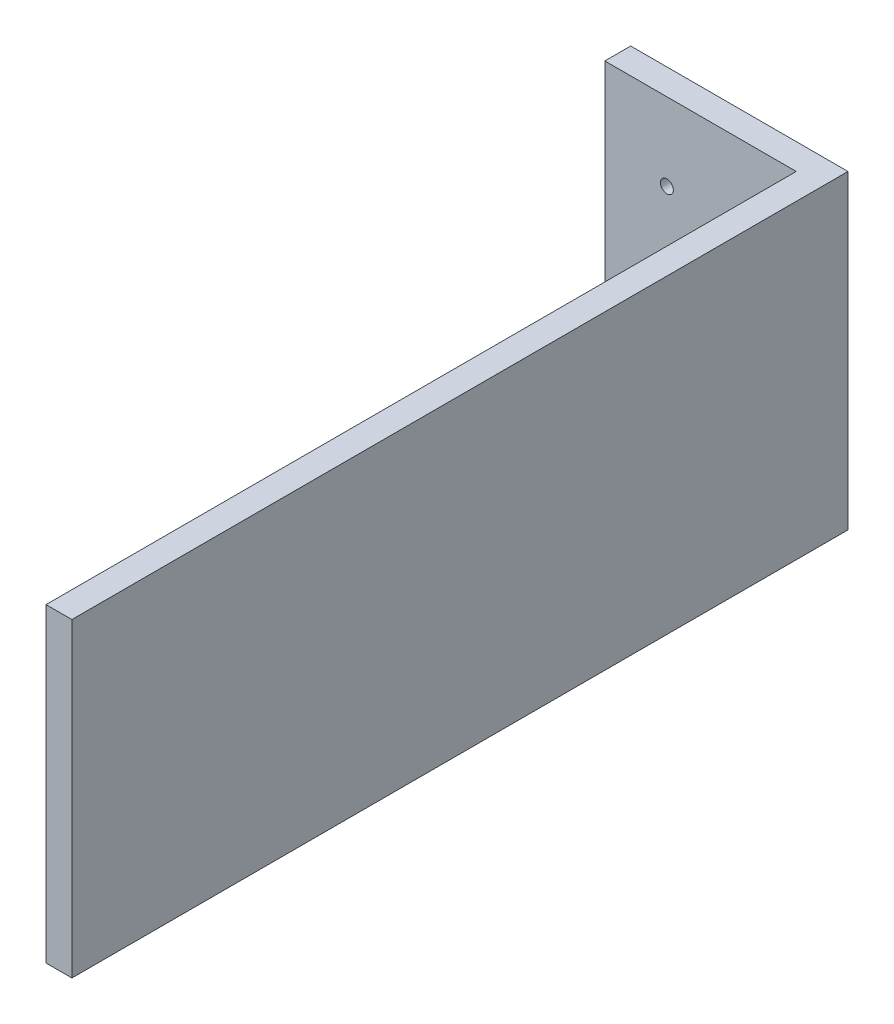
SolidWorks part; units mm, degrees
ref_plane "前视基准面" through (0, 0, 0) normal (0, 0, 1) x (1, 0, 0)
ref_plane "上视基准面" through (0, 0, 0) normal (0, 1, 0) x (1, 0, 0)
ref_plane "右视基准面" through (0, 0, 0) normal (1, 0, 0) x (0, 0, -1)
sketch "草图1" plane through (0, 0, 0) normal (0, 0, 1) x (1, 0, 0)
  line L0 (-788.4059, 0) -> (38631.8872, 0) construction
  line L1 (0, -788.4059) -> (0, 38631.8872) construction
  line L2 (16.1199, 30) -> (16.1199, -30)
  line L3 (-20.8801, 30) -> (21.1199, 30)
  line L4 (-20.8801, 30) -> (-20.8801, -30)
  line L5 (-20.8801, -30) -> (21.1199, -30)
  line L6 (21.1199, 30) -> (21.1199, -30)
  line L7 (16.1199, 30) -> (16.1199, -30) construction
  dimension "D1" = 30
  dimension "D2" = 60
  dimension "D3" = 5
  dimension "D4" = 37
  dimension "D5" = 0
extrude "凸台-拉伸1" add sketch "草图1" along normal blind 5 contours L4 L5 L2 L3 region at (-2.3801, 0, 0)
extrude "凸台-拉伸2" add sketch "草图1<3>" along normal blind 150 contours L6 L3 L2 L5 region at (18.6199, 0, 0)
sketch "草图1<3>" plane through (0, 0, 0) normal (0, 0, 1) x (1, 0, 0) same geometry as "草图1"
sketch "草图2" plane through (0, 0, 5) normal (0, 0, 1) x (1, 0, 0)
  line L0 (-20.8801, 30) -> (-20.8801, -30) construction
  line L1 (-20.8801, 30) -> (16.1199, 30) construction
  circle A0 centre (-8.8801, 15) radius 2
  circle A1 centre (6.1199, 15) radius 2
  dimension "D1" = 12
  dimension "D2" = 15
  dimension "D3" = 15
hole_wizard "M3 螺纹孔的螺纹孔钻头1" positions "3D草图2" profile "草图4" hole size "M3" standard "GB" end condition through all
sketch3d "3D草图2"
  point P0 (-8.8801, 15, 5)
  point P3 (6.1199, 15, 5)
sketch "草图4" plane through (-8.8801, 15, 5) normal (1, 0, 0) x (0, -1, 0)
  line L0 (0, 0) -> (0, 5)
  line L1 (0, 5) -> (1.25, 5)
  line L2 (1.25, 5) -> (1.25, 0)
  line L5 (1.25, 0) -> (0, 0)
  line L11 (0, -6.35) -> (0, 107.95) construction
  dimension "通孔孔直径" = 2.5
  dimension "通孔孔深度" = 5
mirror "镜向1" about plane through (0, 0, 0) normal (0, 1, 0) of "M3 螺纹孔的螺纹孔钻头1"
